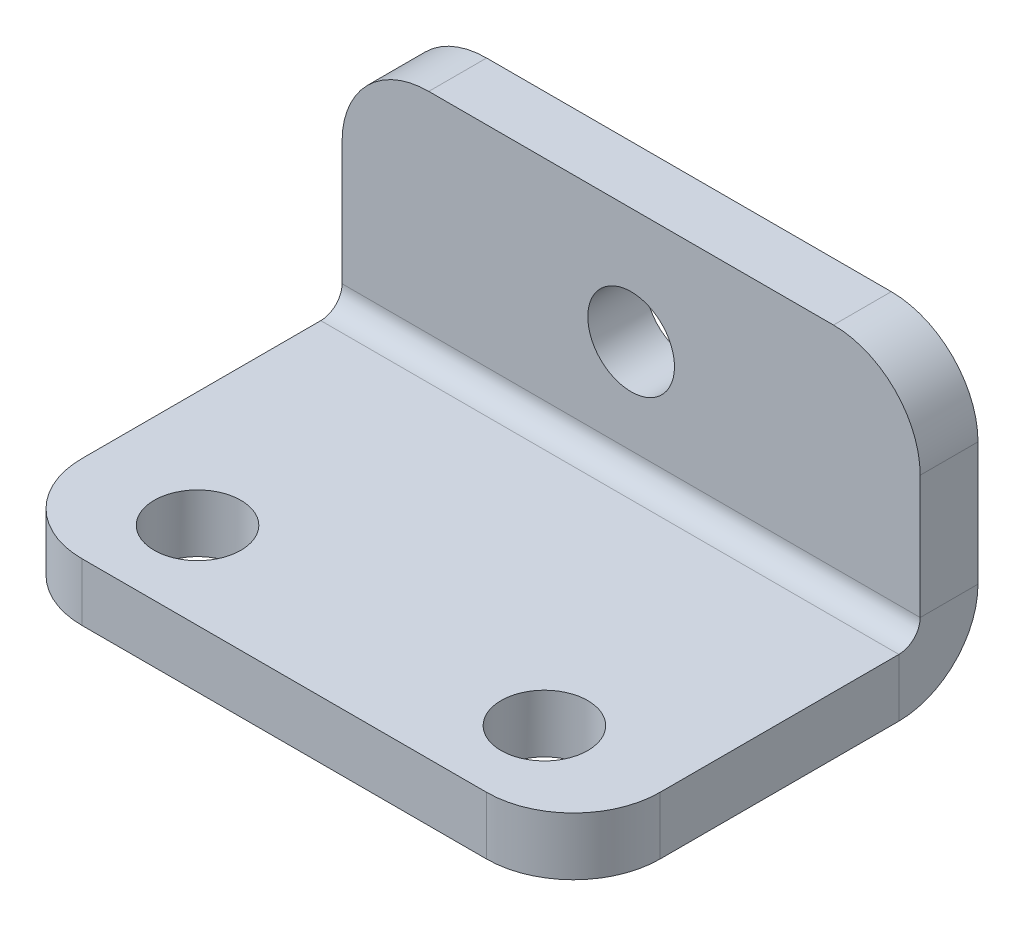
SolidWorks part; units mm, degrees
note: The reader was unsure of these and kept them because the rebuilt part matched: bend radius of "BaseBend1".
material "Thornel Mat VMA"
ref_plane "Front" through (0, 0, 0) normal (0, 0, 1) x (1, 0, 0)
ref_plane "Top" through (0, 0, 0) normal (0, 1, 0) x (1, 0, 0)
ref_plane "Right" through (0, 0, 0) normal (1, 0, 0) x (0, 0, -1)
sketch "Sketch1" plane through (0, 0, 0) normal (1, 0, 0) x (0, 0, -1)
  line L0 (0, 8) -> (0, 0)
  line L1 (0, 0) -> (-12, 0)
  dimension "D1" = 8
  dimension "D2" = 12
base flange "Base-Flange1" sketch "Sketch1" end condition mid plane depth 20 reverse direction no thickness 2 reverse thickness direction yes bend radius 0.7366
bend "BaseBend1" bend radius 0.7366 bend angle 90 parameters "D5"=1
fillet "Fillet1" radius 3 4 edges at (-10, -1, 12) (-10, 8, -1) (10, 8, -1) (10, -1, 12)
sketch "Sketch6" plane through (0, 0, 0) normal (0, 1, 0) x (1, 0, 0)
  line L0 (0, -12) -> (0, -9) construction
  line L1 (7, -12) -> (-7, -12) construction
  line L2 (-6, -9) -> (6, -9) construction
  circle A0 centre (6, -9) radius 1.5
  circle A1 centre (-6, -9) radius 1.5
  dimension "D1" = 3
  dimension "D2" = 3
  dimension "D3" = 12
extrude "Cut-Extrude1" cut sketch "Sketch6" against normal blind 10 normal cut yes
sketch "Sketch7" plane through (0, 0, 0) normal (0, 0, 1) x (1, 0, 0)
  line L0 (7, 8) -> (-7, 8) construction
  line L1 (0, 8) -> (0, 4) construction
  circle A0 centre (0, 4) radius 1.5
  dimension "D1" = 3
  dimension "D2" = 4
extrude "Cut-Extrude2" cut sketch "Sketch7" against normal blind 10 normal cut yes
sketch "Bend-Lines1" [suppressed] plane through (0, 0, 0) normal (0, 1, 0) x (-1, 0, 0)
sketch "Bounding-Box1" [suppressed] plane through (0, 0, 0) normal (0, 1, 0) x (-1, 0, 0)
sheet metal parameters "Sheet-Metal1" thickness 2 parameters "D1"=0.7366
flat pattern "Flat-Pattern1" [suppressed]
sketch "Bend-Lines2" plane through (0, 0, 0) normal (0, -1, 0) x (1, 0, 0)
  line L0 (20, 1.3727) -> (0, 1.3727) construction
  line L1 (20, 1.3727) -> (0, 1.3727) construction
sketch3d "Bounding-Box2" [suppressed]
  line L0 (0, 12, 0) -> (-20, 12, 0) construction
  line L1 (0, -5.2546, 0) -> (-20, -5.2546, 0) construction
  line L2 (0, 12, 0) -> (0, -5.2546, 0) construction
  line L3 (-20, 12, 0) -> (-20, -5.2546, 0) construction
bend of the flat pattern "Flatten-<BaseBend1>1"
sheet metal parameters "Sheet-Metal2" thickness 2 parameters "D1"=0.7366
flat pattern "Flat-Pattern1" [suppressed]
sketch "Bend-Lines2" plane through (0, -2, 0) normal (0, -1, 0) x (-1, 0, 0)
  line L0 (-10, 0.6273) -> (10, 0.6273) construction
  line L1 (-10, 0.6273) -> (10, 0.6273) construction
sketch3d "Bounding-Box2" [suppressed]
  line L0 (20, 9.2546, 0) -> (20, -12, 0) construction
  line L1 (0, 9.2546, 0) -> (0, -12, 0) construction
  line L2 (20, 9.2546, 0) -> (0, 9.2546, 0) construction
  line L3 (20, -12, 0) -> (0, -12, 0) construction
bend of the flat pattern "Flatten-<BaseBend1>1"
sketch "Sketch7-1" [suppressed] plane through (0, 0, -1.2546) normal (0, 1, 0) x (1, 0, 0)
  line L0 (7, 8) -> (-7, 8) construction
  line L1 (0, 8) -> (0, 4) construction
  circle A0 centre (0, 4) radius 1.5
  dimension "D1" = 3
  dimension "D2" = 4
sheet metal parameters "Sheet-Metal3" thickness 2 parameters "D1"=0.7366
flat pattern "Flat-Pattern1" [suppressed]
sketch "Bend-Lines2" plane through (0, -2, 0) normal (0, -1, 0) x (1, 0, 0)
  line L0 (10, -0.6273) -> (-10, -0.6273) construction
  line L1 (10, -0.6273) -> (-10, -0.6273) construction
sketch3d "Bounding-Box2" [suppressed]
  line L0 (-20, -9.2546, 0) -> (-20, 12, 0) construction
  line L1 (0, -9.2546, 0) -> (0, 12, 0) construction
  line L2 (-20, -9.2546, 0) -> (0, -9.2546, 0) construction
  line L3 (-20, 12, 0) -> (0, 12, 0) construction
bend of the flat pattern "Flatten-<BaseBend1>1"
sketch "Sketch7-1" [suppressed] plane through (0, 0, -1.2546) normal (0, 1, 0) x (1, 0, 0)
  line L0 (7, 8) -> (-7, 8) construction
  line L1 (0, 8) -> (0, 4) construction
  circle A0 centre (0, 4) radius 1.5
  dimension "D1" = 3
  dimension "D2" = 4
